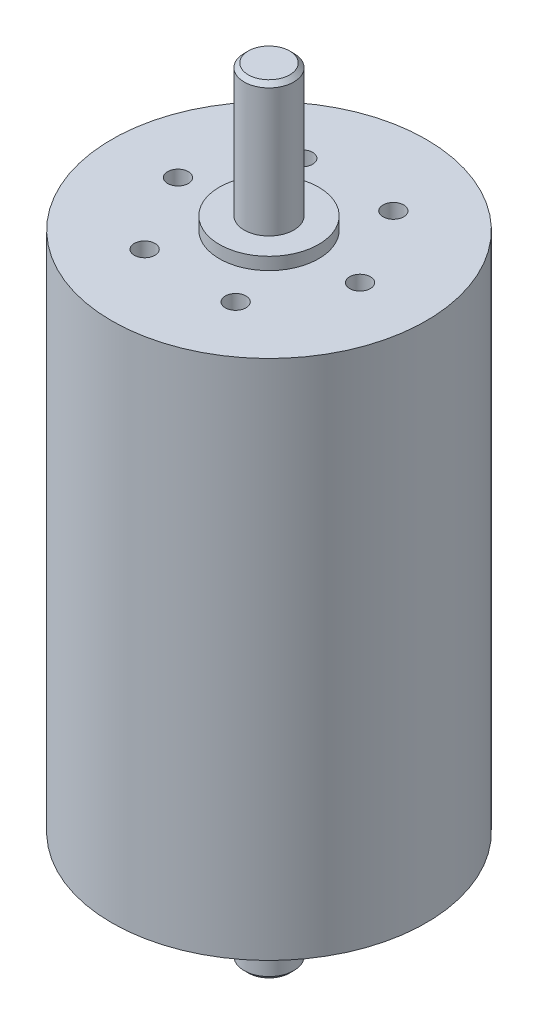
SolidWorks part; units mm, degrees
ref_plane "Face" through (0, 0, 0) normal (0, 0, 1) x (1, 0, 0)
ref_plane "Dessus" through (0, 0, 0) normal (0, 1, 0) x (1, 0, 0)
ref_plane "Droite" through (0, 0, 0) normal (1, 0, 0) x (0, 0, -1)
sketch "Esquisse1" plane through (0, 0, 0) normal (0, 0, 1) x (1, 0, 0)
  line L0 (0, 0) -> (0, 94)
  line L1 (0, 94) -> (3, 94)
  line L2 (3, 94) -> (3, 78)
  line L3 (3, 78) -> (6, 78)
  line L4 (6, 78) -> (6, 76.5)
  line L5 (6, 76.5) -> (19, 76.5)
  line L6 (19, 76.5) -> (19, 13.5)
  line L7 (19, 13.5) -> (6, 13.5)
  line L8 (6, 13.5) -> (6, 12)
  line L9 (6, 12) -> (3, 12)
  line L10 (3, 12) -> (3, 0)
  line L11 (3, 0) -> (0, 0)
  dimension "D1" = 19
  dimension "D2" = 63
  dimension "D3" = 3
  dimension "D4" = 6
  dimension "D5" = 1.5
  dimension "D6" = 12
  dimension "D7" = 16
revolve "Révolution1" add sketch "Esquisse1" angle 360 about L0
sketch "Esquisse2" plane through (0, 13.5, 0) normal (0, -1, 0) x (1, 0, 0)
  line L0 (0, 0) -> (11, 0) construction
  circle A0 centre (11, 0) radius 1.25
  circle A1 centre (5.5, -9.5263) radius 1.25
  circle A2 centre (-5.5, -9.5263) radius 1.25
  circle A3 centre (-11, 0) radius 1.25
  circle A4 centre (-5.5, 9.5263) radius 1.25
  circle A5 centre (5.5, 9.5263) radius 1.25
  point P4 (-13.3895, 2.0033)
  point P5 (0, 0)
  point P16 (0, 0)
  dimension "D2" = 2.5
  dimension "D1" = 11
  dimension "D3" = 6
extrude "Enlèv. mat.-Extru.1" cut sketch "Esquisse2" against normal blind 3
extrude "Enlèv. mat.-Extru.2" cut sketch "Esquisse2<2>" along normal blind 3 from surface starting at face at (0, 76.5, -6)
sketch "Esquisse2<2>" plane through (0, 13.5, 0) normal (0, -1, 0) x (1, 0, 0) same geometry as "Esquisse2"
chamfer "Chanfrein1" distance 0.5 angle 45 2 edges at (0, 94, -3) (0, 0, -3)
